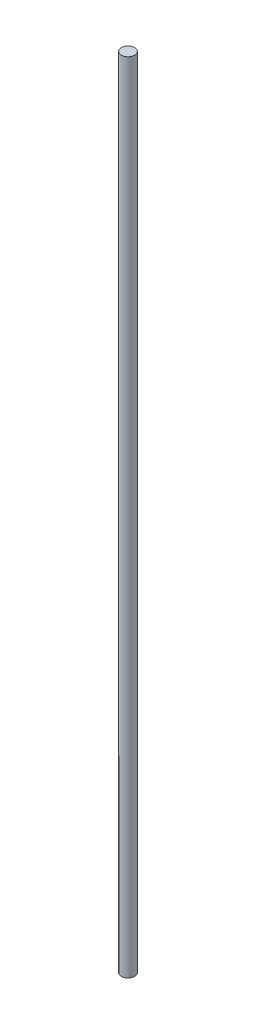
SolidWorks part; units mm, degrees
material "Pine"
ref_plane "Front" through (0, 0, 0) normal (0, 0, 1) x (1, 0, 0)
ref_plane "Top" through (0, 0, 0) normal (0, 1, 0) x (1, 0, 0)
ref_plane "Right" through (0, 0, 0) normal (1, 0, 0) x (0, 0, -1)
ref_axis "X" through (-80.9, 0, 0) along (1, 0, 0)
ref_axis "Y" through (0, -50, 0) along (0, 1, 0)
ref_axis "Z" through (0, 0, -80.9) along (0, 0, 1)
sketch "Sketch1" plane through (0, 0, 0) normal (0, 1, 0) x (1, 0, 0)
  circle A0 centre (0, 0) radius 1.5
  dimension "D1" = 3
extrude "Boss-Extrude1" add sketch "Sketch1" along normal mid plane 175
sketch "Sketch2" plane through (0, 87.5, 0) normal (0, 1, 0) x (1, 0, 0)
  circle A1 centre (0, 0) radius 1.5
  circle A2 centre (0, 0) radius 1.5
  dimension "D1" = 0
extrude "Boss-Extrude2" add sketch "Sketch2" along normal blind 6
